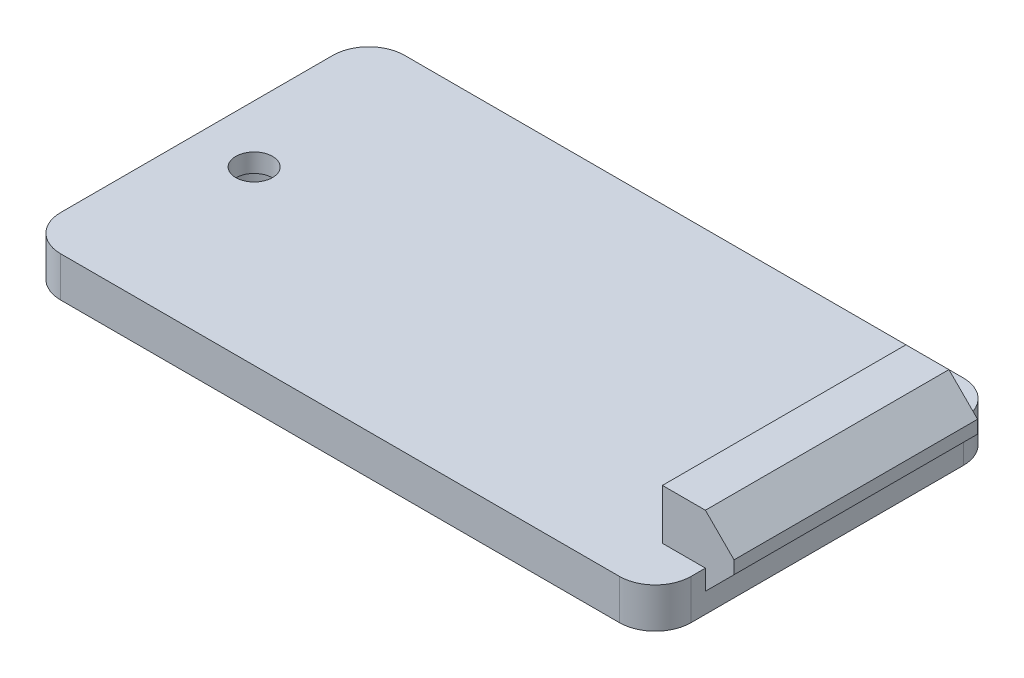
SolidWorks part; units mm, degrees
ref_plane "Front Plane" through (0, 0, 0) normal (0, 0, 1) x (1, 0, 0)
ref_plane "Top Plane" through (0, 0, 0) normal (0, 1, 0) x (1, 0, 0)
ref_plane "Right Plane" through (0, 0, 0) normal (1, 0, 0) x (0, 0, -1)
sketch "Sketch1" plane through (0, 0, 0) normal (0, 1, 0) x (1, 0, 0)
  line L0 (0, 15.24) -> (55.88, 15.24) construction
  line L1 (3.175, 0) -> (52.705, 0)
  line L2 (0, 3.175) -> (0, 27.305)
  line L3 (3.175, 30.48) -> (52.705, 30.48)
  line L4 (55.88, 3.175) -> (55.88, 27.305)
  arc A0 (3.175, 30.48) -> (0, 27.305) centre (3.175, 27.305) ccw
  arc A1 (55.88, 27.305) -> (52.705, 30.48) centre (52.705, 27.305) ccw
  arc A2 (52.705, 0) -> (55.88, 3.175) centre (52.705, 3.175) ccw
  arc A3 (0, 3.175) -> (3.175, 0) centre (3.175, 3.175) ccw
  circle A4 centre (5.08, 15.24) radius 1.632
  dimension "D3" = 6.35
  dimension "D1" = 3.2639
  dimension "D2" = 5.08
  dimension "D4" = 3.175
  dimension "D5" = 3.175
  dimension "D6" = 49.53
  dimension "D7" = 24.13
extrude "Boss-Extrude1" add sketch "Sketch1" along normal blind 3.556
sketch "Sketch2" plane through (0, 0, 0) normal (0, -1, 0) x (1, 0, 0)
  circle A0 centre (5.08, -15.24) radius 3.175
  circle A1 centre (5.08, -15.24) radius 1.6319
  dimension "D1" = 6.35
extrude "Cut-Extrude1" cut sketch "Sketch2" against normal blind 1.905
sketch "Sketch3" plane through (55.88, 0, 0) normal (1, 0, 0) x (0, 0, -1)
  line L0 (3.175, 3.556) -> (3.175, 0) construction
  line L1 (4.445, 1.5875) -> (26.035, 1.5875)
  line L2 (4.445, 1.5875) -> (4.445, 8.1915)
  line L3 (4.445, 8.1915) -> (26.035, 8.1915)
  line L4 (26.035, 1.5875) -> (26.035, 8.1915)
  line L5 (27.305, 3.556) -> (27.305, 0) construction
  line L6 (3.175, 0) -> (27.305, 0) construction
  dimension "D1" = 1.27
  dimension "D2" = 1.27
  dimension "D3" = 1.5875
  dimension "D4" = 6.604
extrude "Boss-Extrude2" add sketch "Sketch3" along normal blind 2.54
chamfer "Chamfer1" distance 2.7305 angle 45 2 edges at (58.42, 1.5875, -15.24) (58.42, 8.1915, -15.24)
sketch "Sketch4" plane through (55.88, 0, 0) normal (-1, 0, 0) x (0, 0, 1)
  line L5 (-26.035, 8.001) -> (-4.445, 8.001)
  line L6 (-26.035, 8.001) -> (-26.035, 3.556)
  line L7 (-26.035, 3.556) -> (-4.445, 3.556)
  line L8 (-4.445, 8.001) -> (-4.445, 3.556)
extrude "Boss-Extrude3" add sketch "Sketch4" along normal blind 3.81
sketch "Sketch5" plane through (0, 0, 0) normal (0, -1, 0) x (1, 0, 0)
  line L0 (12.7, -9.9279) -> (12.7, -30.48) construction
  line L2 (52.705, -30.48) -> (3.175, -30.48) construction
  line L3 (0, -27.305) -> (0, -3.175) construction
  line L4 (0, -15.24) -> (55.88, -15.24) construction
  line L5 (55.88, -26.035) -> (55.88, -4.445) construction
  line L6 (11.1125, -8.89) -> (11.1433, -21.9013)
  line L7 (14.2875, -8.89) -> (14.2567, -21.9013)
  arc A0 (14.2875, -8.89) -> (11.1125, -8.89) centre (12.7, -8.89) ccw
  arc A1 (11.1433, -21.9013) -> (14.2567, -21.9013) centre (12.7, -21.59) ccw
  dimension "D2" = 3.175
  dimension "D3" = 3.175
  dimension "D1" = 12.7
  dimension "D4" = 12.7
  dimension "D5" = 6.35
extrude "Cut-Extrude2" cut sketch "Sketch5" against normal blind 1.778
sketch "Sketch6" plane through (0, 0, 0) normal (0, -1, 0) x (1, 0, 0)
  line L0 (14.2807, -11.7475) -> (55.88, -11.7475) construction
  line L1 (14.2567, -21.9013) -> (14.2875, -8.89) construction
  line L2 (55.88, -26.035) -> (55.88, -4.445) construction
  line L3 (52.705, -30.48) -> (3.175, -30.48) construction
  text T0 "<b>PGM PIN</b>" font "Arial Rounded MT Bold" height 6.35
  dimension "D1" = 18.7325
extrude "Cut-Extrude3" cut sketch "Sketch6" against normal blind 1.016
